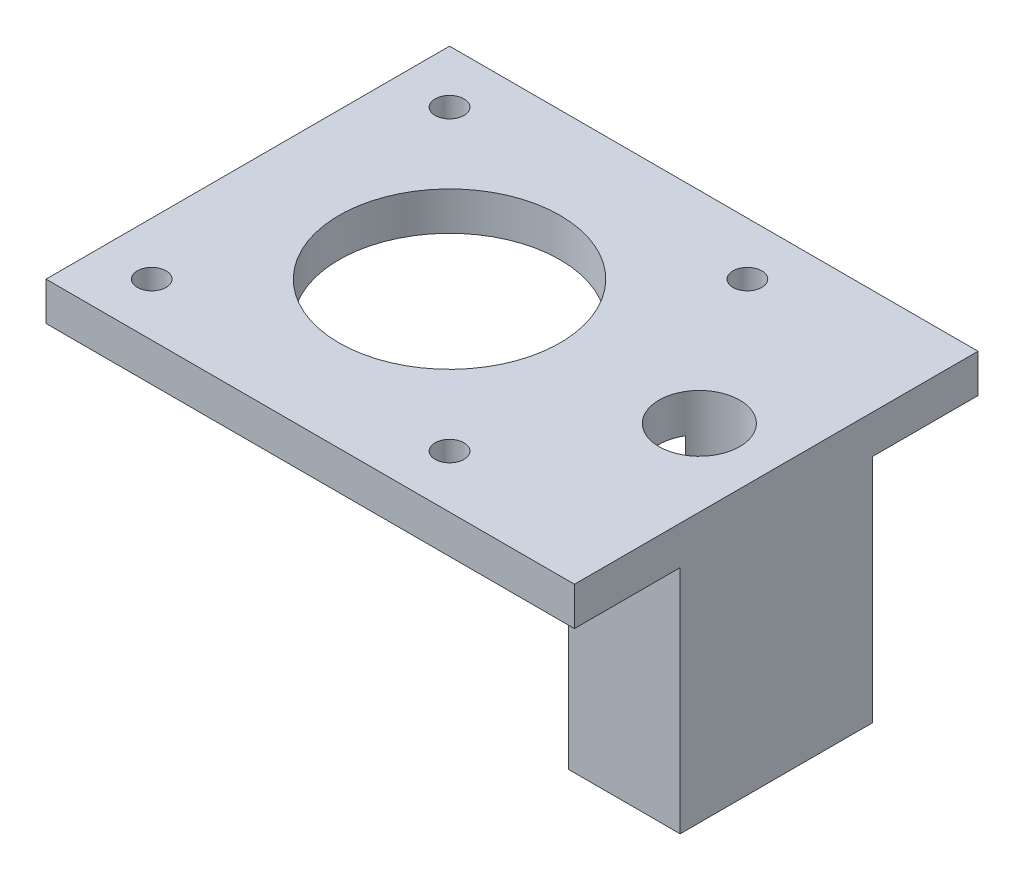
SolidWorks part; units mm, degrees
ref_plane "Front Plane" through (0, 0, 0) normal (0, 0, 1) x (1, 0, 0)
ref_plane "Top Plane" through (0, 0, 0) normal (0, 1, 0) x (1, 0, 0)
ref_plane "Right Plane" through (0, 0, 0) normal (1, 0, 0) x (0, 0, -1)
sketch "Sketch1" plane through (0, 0, 0) normal (0, 1, 0) x (1, 0, 0)
  line L0 (0, 21) -> (55, 21) construction
  line L1 (0, 0) -> (55, 0)
  line L2 (0, 0) -> (0, 42)
  line L3 (0, 42) -> (55, 42)
  line L4 (55, 0) -> (55, 42)
  line L5 (21, 42) -> (21, 0) construction
  circle A0 centre (47, 21) radius 4.2
  circle A1 centre (21, 21) radius 11.5
  circle A2 centre (5.5, 36.5) radius 1.5
  circle A3 centre (36.5, 36.5) radius 1.5
  circle A4 centre (5.5, 5.5) radius 1.5
  circle A5 centre (36.5, 5.5) radius 1.5
  point P8 (55, 21)
  dimension "D2" = 23
  dimension "D4" = 8.4
  dimension "D9" = 3
  dimension "D1" = 26
  dimension "D3" = 42
  dimension "D5" = 21
  dimension "D6" = 55
  dimension "D7" = 15.5
  dimension "D8" = 15.5
extrude "Boss-Extrude1" add sketch "Sketch1" along normal blind 4
sketch "Sketch2" plane through (0, 0, 0) normal (0, -1, 0) x (1, 0, 0)
  line L0 (0, 0) -> (55, 0) construction
  line L1 (40.4, 0) -> (43.4, 0)
  line L2 (40.4, 0) -> (40.4, -42)
  line L3 (40.4, -42) -> (43.4, -42)
  line L4 (43.4, 0) -> (43.4, -42)
  line L5 (55, -42) -> (0, -42) construction
  line L6 (55, 0) -> (55, -42) construction
  line L7 (55, -11) -> (43.4, -11)
  line L8 (55, -11) -> (55, -31)
  line L9 (55, -31) -> (43.4, -31)
  line L10 (43.4, -11) -> (43.4, -31)
  circle A0 centre (47, -21) radius 6.6
  circle A1 centre (47, -21) radius 4.2
  circle A2 centre (47, -21) radius 4.2 construction
  point P25 (55, -21)
  point P26 (55, -21)
  circle M7 centre (47, -21) radius 4.2
  line M10 (55, -42) -> (55, 0)
  dimension "D1" = 2.4
  dimension "D2" = 3
  dimension "D3" = 20
extrude "Boss-Extrude2" add sketch "Sketch2" along normal blind 20 contours L4 A0 L10 M7 | A0 L10 L9 L7 L4 M10 region at (49.2, 0, -11.2312) region at (50.0669, 0, -15.3449)
sketch "Sketch3" plane through (0, -20, 0) normal (0, -1, 0) x (1, 0, 0)
  line L1 (55, -31) -> (43.4, -31)
  line L2 (55, -31) -> (55, -11)
  line L3 (55, -11) -> (43.4, -11)
  line L4 (43.4, -31) -> (43.4, -11)
extrude "Boss-Extrude3" add sketch "Sketch3" along normal blind 4
equation "\"8mm hole\" = 8.4mm"
equation "\"22mm hole\"= 23mm"
equation "\"D2@Sketch1\"=\"22mm hole\""
equation "\"D4@Sketch1\"=\"8mm hole\""
